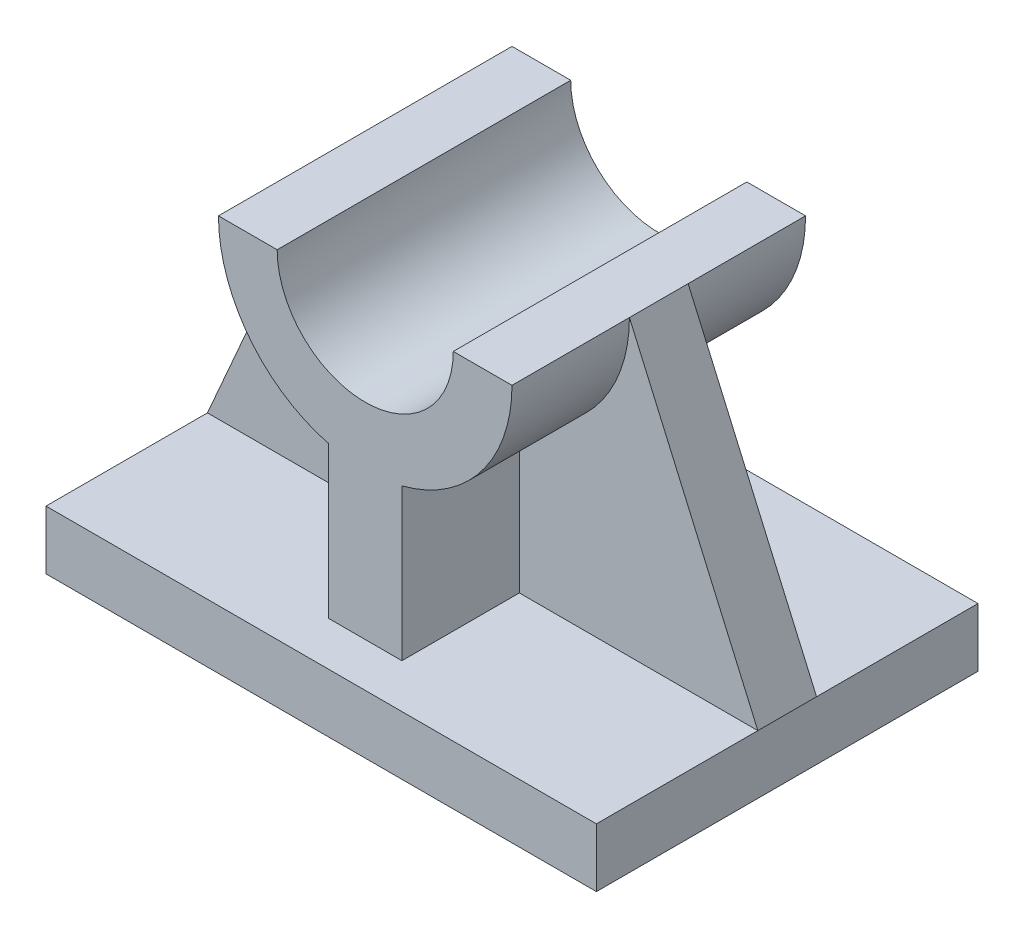
SolidWorks part; units mm, degrees
ref_plane "Front Plane" through (0, 0, 0) normal (0, 0, 1) x (1, 0, 0)
ref_plane "Top Plane" through (0, 0, 0) normal (0, 1, 0) x (1, 0, 0)
ref_plane "Right Plane" through (0, 0, 0) normal (1, 0, 0) x (0, 0, -1)
other "Center of Mass"
sketch "Sketch2" plane through (0, 0, 0) normal (0, 0, 1) x (1, 0, 0)
  line L0 (-5, 4) -> (37.5, 4)
  line L1 (-37.5, 4) -> (-5, 4)
  line L2 (-37.5, 4) -> (-37.5, -4)
  line L3 (-37.5, -4) -> (37.5, -4)
  line L4 (37.5, 4) -> (37.5, -4)
  line L5 (-37.5, 4) -> (37.5, -4) construction
  line L6 (-37.5, -4) -> (37.5, 4) construction
  line L8 (-5, 24.6351) -> (-5, 4)
  line L10 (5, 24.6351) -> (5, 4)
  line L11 (0, 44) -> (0, -10.8855) construction
  line L12 (-12, 44) -> (-20, 44)
  line L13 (12, 44) -> (20, 44)
  arc A0 (5, 24.6351) -> (20, 44) centre (0, 44) ccw
  arc A1 (-12, 44) -> (12, 44) centre (0, 44) ccw
  circle A2 centre (0, 44) radius 20 construction
  arc A3 (-20, 44) -> (-5, 24.6351) centre (0, 44) ccw
  circle A4 centre (0, 44) radius 12 construction
  point P0 (0, 0)
  point P19 (0, 44)
  dimension "D4" = 20
  dimension "D5" = 12
  dimension "D1" = 8
  dimension "D2" = 75
  dimension "D3" = 40
  dimension "D6" = 10
extrude "Boss-Extrude1" add sketch "Sketch2" along normal mid plane 52 contours L1 L2 L3 L4 L0
extrude "Boss-Extrude2" add sketch "Sketch2<3>" along normal mid plane 40 contours L12 A3 L8 L0 L10 A0 L13 A1 region at (0, 27.0809, 0)
sketch "Sketch2<3>" plane through (0, 0, 0) normal (0, 0, 1) x (1, 0, 0) same geometry as "Sketch2"
sketch "Sketch6" plane through (0, 0, 0) normal (0, 0, 1) x (1, 0, 0)
  line L0 (20, 44) -> (37.5, 4)
  line L1 (12, 44) -> (20, 44) construction
  arc A0 (5, 24.6351) -> (20, 44) centre (0, 44) ccw construction
rib "Rib1" sketch "Sketch6" sketch "Sketch6" thickness 8 extrusion direction parallel to sketch draft on no parameters "D1"=8
sketch "Sketch7" plane through (0, 0, 0) normal (0, 0, 1) x (1, 0, 0)
  line L0 (-20, 44) -> (-37.5, 4)
  line L1 (-12, 44) -> (-20, 44) construction
  arc A0 (-20, 44) -> (-5, 24.6351) centre (0, 44) ccw construction
rib "Rib2" sketch "Sketch7" sketch "Sketch7" thickness 8 extrusion direction parallel to sketch draft on no parameters "D1"=8
other "Center of Mass Reference Point1"
